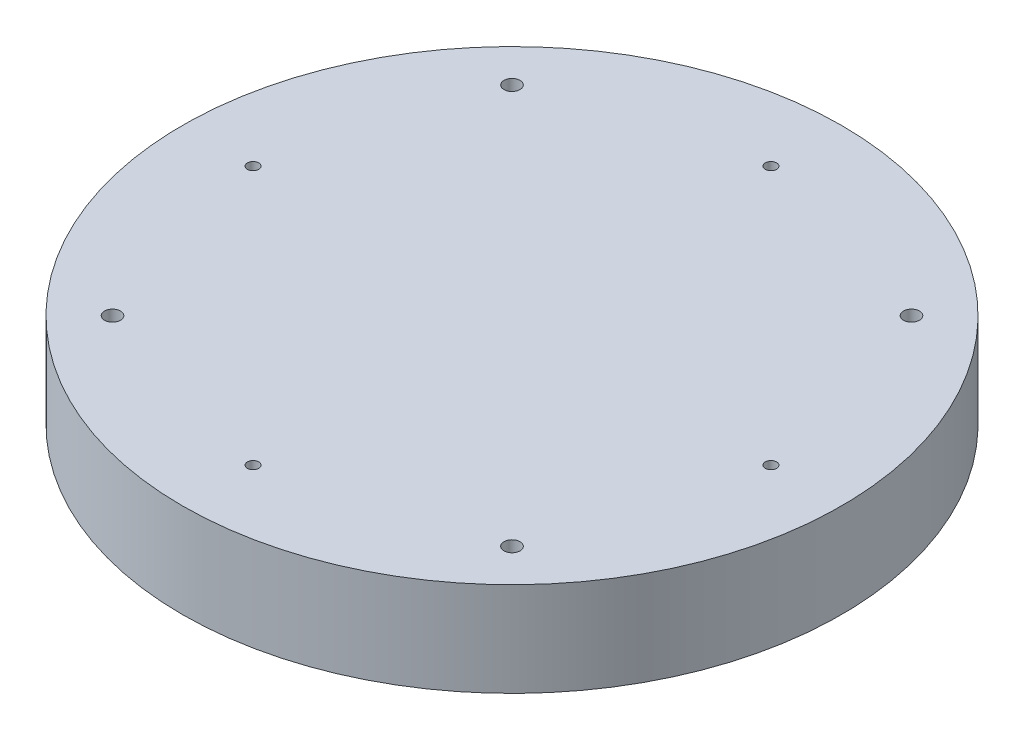
SolidWorks part; units mm, degrees
ref_plane "Front Plane" through (0, 0, 0) normal (0, 0, 1) x (1, 0, 0)
ref_plane "Top Plane" through (0, 0, 0) normal (0, 1, 0) x (1, 0, 0)
ref_plane "Right Plane" through (0, 0, 0) normal (1, 0, 0) x (0, 0, -1)
sketch "Sketch1" plane through (0, 0, 0) normal (0, 1, 0) x (1, 0, 0)
  circle A0 centre (0, 0) radius 175
extrude "Boss-Extrude1" add sketch "Sketch1" along normal blind 30
sketch "Sketch2" plane through (0, 30, 0) normal (0, 1, 0) x (1, 0, 0)
  line L1 (106.066, -106.066) -> (-106.066, -106.066)
  line L2 (106.066, -106.066) -> (106.066, 106.066)
  line L3 (106.066, 106.066) -> (-106.066, 106.066)
  line L4 (-106.066, -106.066) -> (-106.066, 106.066)
  line L5 (106.066, -106.066) -> (-106.066, 106.066) construction
  line L6 (106.066, 106.066) -> (-106.066, -106.066) construction
  circle A0 centre (0, 0) radius 150
  point P0 (0, 0)
  dimension "D2" = 300
  dimension "D1" = 90
hole_wizard "Tap Drill for M10x1.5 Tap1" positions "Sketch4" profile "Sketch3" hole size "M10x1.5" standard "ANSI Metric"
sketch "Sketch4" plane through (0, 30, 0) normal (0, 1, 0) x (1, 0, 0)
  point P0 (-106.066, -106.066)
  point P3 (106.066, -106.066)
  point P6 (106.066, 106.066)
  point P9 (-106.066, 106.066)
sketch "Sketch3" plane through (-106.066, 30, 106.066) normal (1, 0, 0) x (0, 0, 1)
  line L0 (0, 0) -> (0, 22.5537)
  line L1 (0, 22.5537) -> (4.25, 20)
  line L2 (4.25, 20) -> (4.25, 0)
  line L5 (4.25, 0) -> (0, 0)
  line L10 (0, 22.5537) -> (-4.25, 20) construction
  line L11 (0, -6.35) -> (0, 107.95) construction
  dimension "Hole Dia." = 8.5
  dimension "Hole Depth" = 20
  dimension "Drill Angle" = 118
sketch "Sketch7" plane through (0, 0, 0) normal (0, -1, 0) x (1, 0, 0)
  circle A0 centre (0, 0) radius 175
extrude "Boss-Extrude2" add sketch "Sketch7" along normal blind 20
sketch "Sketch8" plane through (0, -20, 0) normal (0, -1, 0) x (1, 0, 0)
  line L0 (-150, 0) -> (203.4414, 0) construction
  circle A0 centre (0, 0) radius 150
ref_axis "Axis1" through (0, 30, 0) along (0, -1, 0)
sketch "Sketch10" plane through (0, -20, 0) normal (0, -1, 0) x (1, 0, 0)
  circle A0 centre (0, 0) radius 65.786
  point P3 (0, 65.786)
  point P4 (65.786, 0)
  point P5 (0, -65.786)
  point P6 (-65.786, 0)
sketch "Sketch14" plane through (0, -20, 0) normal (0, -1, 0) x (1, 0, 0)
  circle A0 centre (0, 0) radius 145
  circle A1 centre (145, 0) radius 15
  dimension "D1" = 290
  dimension "D2" = 30
sketch "Sketch15" plane through (0, 30, 0) normal (0, 1, 0) x (1, 0, 0)
  circle A0 centre (0, 0) radius 137.5
  point P3 (0, -137.5)
  point P4 (-137.5, 0)
  point P5 (137.5, 0)
  point P6 (0, 137.5)
  dimension "D1" = 275
hole_wizard "Ø6.0 (6) Diameter Hole1" positions "Sketch19" profile "Sketch20" hole size "Ø6.0" standard "ANSI Metric" end condition through all
sketch "Sketch19" plane through (0, 30, 0) normal (0, 1, 0) x (1, 0, 0)
  point P0 (-137.5, 0)
  point P3 (0, -137.5)
  point P6 (137.5, 0)
  point P9 (0, 137.5)
sketch "Sketch20" plane through (-137.5, 30, 0) normal (1, 0, 0) x (0, 0, 1)
  line L0 (0, 0) -> (0, 50)
  line L1 (0, 50) -> (3, 50)
  line L2 (3, 50) -> (3, 0)
  line L5 (3, 0) -> (0, 0)
  line L11 (0, -6.35) -> (0, 107.95) construction
  dimension "Thru Hole Dia." = 6
  dimension "Thru Hole Depth" = 50
sketch "Sketch21" plane through (0, -20, 0) normal (0, -1, 0) x (1, 0, 0)
  line L0 (0.0679, -0.0017) -> (0.0679, 78.4843) construction
  circle A0 centre (0.0679, -0.0017) radius 78.486
  circle A1 centre (78.5031, -0.0017) radius 3.5687
  circle A2 centre (-78.3673, -0.0017) radius 3.5687
  point P7 (0.0679, -0.0017)
  point P8 (0.0679, -78.4877)
  dimension "D1" = 156.972
hole_wizard "Tap Drill for M7x1.0 Tap2" positions "Sketch23" profile "Sketch22" hole size "M7x1.0" standard "ANSI Metric"
sketch "Sketch23" plane through (0, -20, 0) normal (0, -1, 0) x (-1, 0, 0)
  point P0 (78.3673, 0.0017)
  point P3 (-0.0679, -78.4843)
  point P6 (-78.5031, 0.0017)
  point P9 (-0.0679, 78.4877)
sketch "Sketch22" plane through (-78.3673, -20, -0.0017) normal (1, 0, 0) x (0, 0, -1)
  line L0 (0, 0) -> (0, 21.8026)
  line L1 (0, 21.8026) -> (3, 20)
  line L2 (3, 20) -> (3, 0)
  line L5 (3, 0) -> (0, 0)
  line L10 (0, 21.8026) -> (-3, 20) construction
  line L11 (0, -6.35) -> (0, 107.95) construction
  dimension "Hole Dia." = 6
  dimension "Hole Depth" = 20
  dimension "Drill Angle" = 118
sketch "Sketch24" plane through (0, 30, 0) normal (0, 1, 0) x (1, 0, 0)
  line L0 (106.066, 106.066) -> (-106.066, -106.066) construction
  line L1 (-106.066, 106.066) -> (106.066, -106.066) construction
